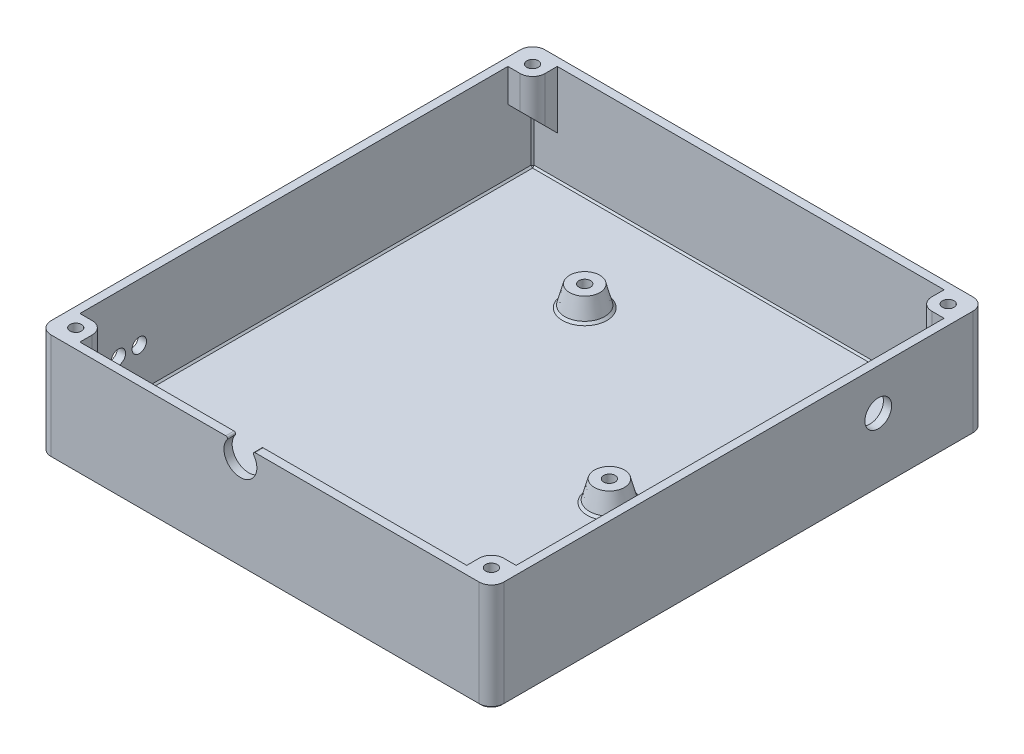
SolidWorks part; units mm, degrees
ref_plane "前视基准面" through (0, 0, 0) normal (0, 0, 1) x (1, 0, 0)
ref_plane "上视基准面" through (0, 0, 0) normal (0, 1, 0) x (1, 0, 0)
ref_plane "右视基准面" through (0, 0, 0) normal (1, 0, 0) x (0, 0, -1)
other "Configuration Table"
sketch "草图1" plane through (0, 0, 0) normal (0, 1, 0) x (1, 0, 0)
  line L1 (0, 0) -> (110, 0)
  line L2 (0, 0) -> (0, 120)
  line L3 (0, 120) -> (110, 120)
  line L4 (110, 0) -> (110, 120)
  dimension "D1" = 120
  dimension "D2" = 110
extrude "凸台-拉伸1" add sketch "草图1" along normal blind 2
sketch "草图2" plane through (0, 2, 0) normal (0, 1, 0) x (1, 0, 0)
  line L0 (0, 0) -> (110, 0) construction
  line L1 (0, 120) -> (0, 0) construction
  line L2 (110, 120) -> (0, 120) construction
  line L3 (110, 0) -> (110, 120) construction
  circle A0 centre (82.1, 56.57) radius 5
  circle A1 centre (38.1, 94.57) radius 5
  circle A2 centre (23.1, 13.57) radius 5
  point P12 (55, 120)
  point P15 (110, 60)
  point P16 (0, 60)
  point P17 (55, 0)
  dimension "D1" = 10
  dimension "D2" = 10
  dimension "D3" = 10
  dimension "D4" = 46.43
  dimension "D5" = 31.9
  dimension "D6" = 16.9
  dimension "D7" = 34.57
  dimension "D8" = 27.1
  dimension "D9" = 3.43
extrude "凸台-拉伸2" add sketch "草图2" along normal blind 5 draft 15
sketch "草图3" plane through (0, 7, 0) normal (0, 1, 0) x (1, 0, 0)
  circle A1 centre (82.1, 56.57) radius 1.4
  circle A2 centre (38.1, 94.57) radius 1.4
  circle A3 centre (23.1, 13.57) radius 1.4
  circle A4 centre (23.1, 13.57) radius 3.6603 construction
  circle A5 centre (38.1, 94.57) radius 3.6603 construction
  circle A6 centre (82.1, 56.57) radius 3.6603 construction
  dimension "D1" = 2.8
  dimension "D2" = 2.8
  dimension "D3" = 2.8
  dimension "D4" = 0
  dimension "D5" = 0
  dimension "D6" = 0
  dimension "D7" = 0
  dimension "D8" = 0
  dimension "D9" = 0
extrude "切除-拉伸1" cut sketch "草图3" against normal blind 5
sketch "草图4" plane through (0, 2, 0) normal (0, 1, 0) x (1, 0, 0)
  line L9 (2, 118) -> (2, 2)
  line L10 (2, 2) -> (108, 2)
  line L11 (108, 2) -> (108, 118)
  line L12 (108, 118) -> (2, 118)
  line L13 (2, 118) -> (2, 2)
  line L14 (2, 2) -> (108, 2)
  line L15 (108, 2) -> (108, 118)
  line L16 (108, 118) -> (2, 118)
  line L21 (0, 120) -> (0, 0)
  line L22 (0, 0) -> (110, 0)
  line L23 (110, 0) -> (110, 120)
  line L24 (110, 120) -> (0, 120)
  line L25 (0, 120) -> (0, 0)
  line L26 (0, 0) -> (110, 0)
  line L27 (110, 0) -> (110, 120)
  line L28 (110, 120) -> (0, 120)
  dimension "D1" = 2
  dimension "D2" = 0
extrude "凸台-拉伸3" add sketch "草图4" along normal blind 24
sketch "草图5" plane through (0, 26, 0) normal (0, 1, 0) x (1, 0, 0)
  line L1 (2, 118) -> (8, 118)
  line L2 (2, 118) -> (2, 112)
  line L3 (2, 112) -> (8, 112)
  line L4 (8, 118) -> (8, 112)
  line L5 (108, 118) -> (102, 118)
  line L6 (108, 118) -> (108, 112)
  line L7 (108, 112) -> (102, 112)
  line L8 (102, 118) -> (102, 112)
  line L9 (108, 2) -> (102, 2)
  line L10 (108, 2) -> (108, 8)
  line L11 (108, 8) -> (102, 8)
  line L12 (102, 2) -> (102, 8)
  line L13 (2, 2) -> (8, 2)
  line L14 (2, 2) -> (2, 8)
  line L15 (2, 8) -> (8, 8)
  line L16 (8, 2) -> (8, 8)
  dimension "D1" = 6
  dimension "D2" = 6
  dimension "D3" = 6
  dimension "D4" = 6
  dimension "D5" = 6
  dimension "D6" = 6
  dimension "D7" = 6
  dimension "D8" = 6
extrude "凸台-拉伸4" add sketch "草图5" against normal blind 8
chamfer "倒角1" distance 6 angle 45 4 edges at (105, 18, -118) (5, 18, -118) (105, 18, -2) (5, 18, -2)
sketch "草图6" plane through (0, 26, 0) normal (0, 1, 0) x (1, 0, 0)
  line L0 (110, 120) -> (0, 120) construction
  line L1 (0, 120) -> (0, 0) construction
  circle A0 centre (4.5, 115.5) radius 1.4
  circle A1 centre (105.5, 115.5) radius 1.4
  circle A2 centre (105.5, 4.5) radius 1.4
  circle A3 centre (4.5, 4.5) radius 1.4
  dimension "D1" = 4.5
  dimension "D2" = 4.5
  dimension "D3" = 2.8
  dimension "D4" = 2
  dimension "D5" = 2
extrude "切除-拉伸2" cut sketch "草图6" against normal blind 8
fillet "圆角1" radius 3 8 edges at (0, 13, 0) (110, 13, 0) (110, 13, -120) (0, 13, -120) (102, 22, -8) (102, 22, -112) (8, 22, -8) (8, 22, -112)
chamfer "倒角2" distance 0.4 angle 45 8 edges at (109.1213, 0, -0.8787) (110, 0, -60) (109.1213, 0, -119.1213) (55, 0, -120) (0.8787, 0, -119.1213) (0, 0, -60) (0.8787, 0, -0.8787) (55, 0, 0)
chamfer "倒角3" distance 0.4 angle 45 11 edges at (82.1, 2, -61.57) (38.1, 2, -99.57) (23.1, 2, -18.57) (108, 7, -2) (108, 2, -60) (108, 7, -118) (55, 2, -118) (55, 2, -2) (2, 7, -2) (2, 2, -60) (2, 7, -118) first distance on face at (55, 2, -60) first distance on face at (108, 14.5, -60) first distance on face at (2, 14.5, -60)
sketch "草图8" plane through (0, 0, 0) normal (0, 0, 1) x (1, 0, 0)
  line L0 (3, 26) -> (107, 26) construction
  circle A0 centre (49, 23) radius 4
  dimension "D1" = 8
  dimension "D2" = 3
extrude "切除-拉伸3" cut sketch "草图8" against normal blind 3
fillet "圆角2" radius 0.4 2 edges at (46.3542, 26, -1) (51.6458, 26, -1)
sketch "草图9" plane through (108, 0, 0) normal (-1, 0, 0) x (0, 0, 1)
  line L0 (-8, 26) -> (-112, 26) construction
  circle A0 centre (-94, 16) radius 3.25
  point P4 (-60, 26)
  dimension "D1" = 6.5
  dimension "D2" = 10
  dimension "D3" = 34
extrude "切除-拉伸4" cut sketch "草图9" against normal blind 10
sketch "草图10" plane through (2, 0, 0) normal (1, 0, 0) x (0, 0, -1)
  circle A0 centre (22.43, 12.1) radius 1.75
  circle A1 centre (17.35, 12.1) radius 1.75
  dimension "D1" = 3.5
  dimension "D2" = 3.5
extrude "切除-拉伸5" cut sketch "草图10" against normal blind 10
